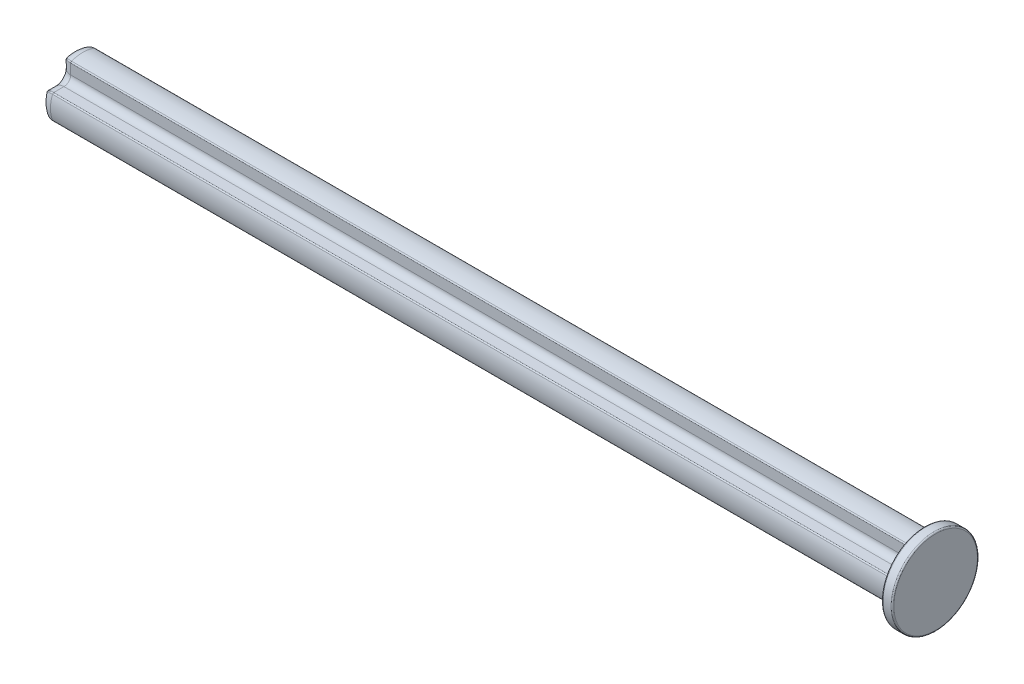
SolidWorks part; units mm, degrees
material "PET"
ref_plane "Alzado" through (0, 0, 0) normal (0, 0, 1) x (1, 0, 0)
ref_plane "Planta" through (0, 0, 0) normal (0, 1, 0) x (1, 0, 0)
ref_plane "Vista lateral" through (0, 0, 0) normal (1, 0, 0) x (0, 0, -1)
sketch "Croquis1" plane through (0, 0, 0) normal (1, 0, 0) x (0, 0, -1)
  line B0 (-1.4, 0.9) -> (-2.2249, 0.9)
  line B1 (0.9, -2.2249) -> (0.9, -1.4)
  line B2 (-0.9, -2.2249) -> (-0.9, -1.4)
  line B3 (2.2249, 0.9) -> (1.4, 0.9)
  line B4 (2.2249, -0.9) -> (1.4, -0.9)
  line B5 (-0.9, 1.4) -> (-0.9, 2.2249)
  line B6 (0.9, 1.4) -> (0.9, 2.2249)
  line B7 (-1.4, -0.9) -> (-2.2249, -0.9)
  arc B8 (-2.2249, 0.9) -> (-2.2249, -0.9) centre (0, 0) ccw
  arc B9 (-1.4, -0.9) -> (-0.9, -1.4) centre (-1.4, -1.4) cw
  arc B10 (0.9, -1.4) -> (1.4, -0.9) centre (1.4, -1.4) cw
  arc B11 (1.4, 0.9) -> (0.9, 1.4) centre (1.4, 1.4) cw
  arc B12 (-0.9, 1.4) -> (-1.4, 0.9) centre (-1.4, 1.4) cw
  arc B13 (0.9, 2.2249) -> (-0.9, 2.2249) centre (0, 0) ccw
  arc B14 (2.2249, -0.9) -> (2.2249, 0.9) centre (0, 0) ccw
  arc B15 (-0.9, -2.2249) -> (0.9, -2.2249) centre (0, 0) ccw
sketch_block_instance "Axle Section Block-1"
sketch_block "Axle Section Block" parameters "D1"=4.8, "D3"=0.5, "D2"=1.8
extrude "Saliente-Extruir1" add sketch "Croquis1" along normal blind 64
sketch "Croquis2" plane through (64, 0, 0) normal (1, 0, 0) x (0, 0, -1)
  circle A0 centre (0, 0) radius 3.2
  dimension "D1" = 6.4
extrude "Saliente-Extruir2" add sketch "Croquis2" against normal blind 0.8
fillet "Redondeo1" radius 0.1 26 edges at (31.6, -2.2249, -0.9) (31.6, -0.9, -2.2249) (31.6, 0.9, -2.2249) (31.6, 2.2249, -0.9) (31.6, -2.2249, 0.9) (31.6, 2.2249, 0.9) (31.6, 0.9, 2.2249) (31.6, -0.9, 2.2249) (63.2, 1.0464, -1.0464) (63.2, 0.9, -1.8124) (63.2, 0, -2.4) (63.2, -0.9, -1.8124) (63.2, -1.0464, -1.0464) (63.2, -1.8124, -0.9) (63.2, -2.4, 0) (63.2, -1.8124, 0.9) (63.2, -1.0464, 1.0464) (63.2, -0.9, 1.8124) (63.2, 0, 2.4) (63.2, 0.9, 1.8124) (63.2, 1.0464, 1.0464) (63.2, 1.8124, 0.9) (63.2, 2.4, 0) (63.2, 1.8124, -0.9) (63.2, 0, -3.2) (64, 0, -3.2)
fillet "Redondeo2" radius 0.8 24 edges at (0, -1.0464, -1.0464) (0, -0.9, -1.7782) (0, -0.8821, -2.2135) (0, 0, -2.4) (0, 0.8821, -2.2135) (0, 0.9, -1.7782) (0, 1.0464, -1.0464) (0, 1.7782, -0.9) (0, 2.2135, -0.8821) (0, 2.4, 0) (0, 2.2135, 0.8821) (0, 1.7782, 0.9) (0, 1.0464, 1.0464) (0, 0.9, 1.7782) (0, 0.8821, 2.2135) (0, 0, 2.4) (0, -0.8821, 2.2135) (0, -0.9, 1.7782) (0, -1.0464, 1.0464) (0, -1.7782, 0.9) (0, -2.2135, 0.8821) (0, -2.4, 0) (0, -2.2135, -0.8821) (0, -1.7782, -0.9)
